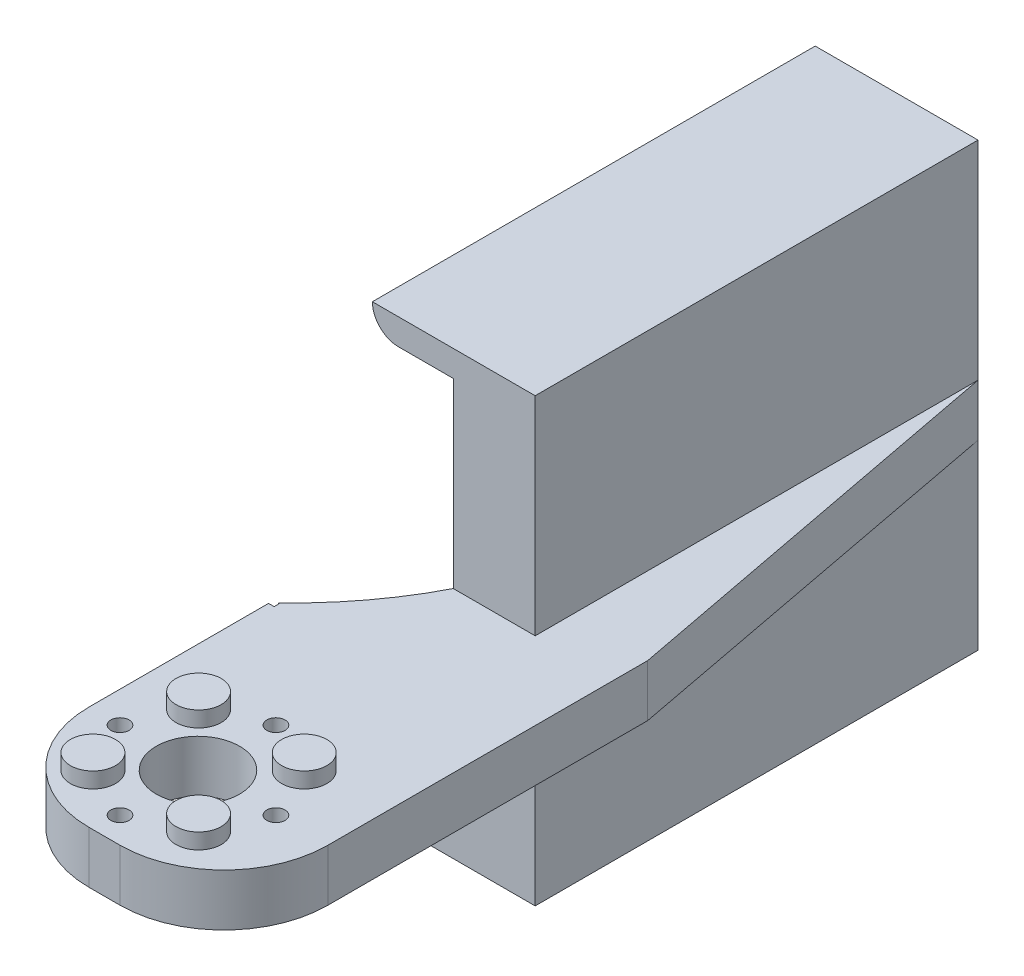
SolidWorks part; units mm, degrees
ref_plane "Front Plane" through (0, 0, 0) normal (0, 0, 1) x (1, 0, 0)
ref_plane "Top Plane" through (0, 0, 0) normal (0, 1, 0) x (1, 0, 0)
ref_plane "Right Plane" through (0, 0, 0) normal (1, 0, 0) x (0, 0, -1)
sketch "Sketch1" plane through (0, 0, 0) normal (0, 1, 0) x (1, 0, 0)
  line L1 (-25, 70) -> (25, 70)
  line L2 (-25, 70) -> (-25, -70)
  line L3 (-25, -70) -> (25, -70)
  line L4 (25, 70) -> (25, -70)
  dimension "D1" = 140
  dimension "D2" = 50
  dimension "D3" = 25
  dimension "D4" = 70
extrude "Boss-Extrude1" add sketch "Sketch1" along normal blind 10
sketch "Sketch2" plane through (0, 10, 0) normal (0, 1, 0) x (1, 0, 0)
  circle A4 centre (-14.25, 0) radius 4.35
  dimension "D1" = 8.7
  dimension "D2" = 14.25
extrude "Boss-Extrude2" add sketch "Sketch2" along normal blind 3
pattern_circular "CirPattern2" count 8 over 360 about axis through (0.1221, 0, 0) along (0, 1, 0) of "Boss-Extrude2"
sketch "Sketch4" plane through (0, 13, 0) normal (0, 1, 0) x (1, 0, 0)
  circle A0 centre (-14.25, 0) radius 4.575
  circle A1 centre (14.4941, 0) radius 4.575
  circle A2 centre (0.1221, -14.3721) radius 4.575
  circle A3 centre (0.1221, 14.3721) radius 4.575
extrude "Cut-Extrude3" cut sketch "Sketch4" against normal blind 3
sketch "Sketch5" plane through (0, 0, -70) normal (0, 0, -1) x (-1, 0, 0)
  line L1 (-25, 10) -> (25, 10)
  line L2 (-25, 10) -> (-25, 0)
  line L3 (-25, 0) -> (25, 0)
  line L4 (25, 10) -> (25, 0)
extrude "Boss-Extrude3" add sketch "Sketch5" along normal blind 70
sketch "Sketch6" plane through (0, 10, 0) normal (0, 1, 0) x (1, 0, 0)
  line L0 (-25, 140) -> (-25, -70) construction
  line L1 (25, -70) -> (-25, -70)
  line L2 (25, -70) -> (25, -20)
  line L3 (25, -20) -> (-25, -20)
  line L4 (-25, -70) -> (-25, -20)
  dimension "D1" = 50
extrude "Cut-Extrude4" cut sketch "Sketch6" against normal blind 10
sketch "Sketch7" plane through (0, 10, 0) normal (0, 1, 0) x (1, 0, 0)
  circle A0 centre (15, 0) radius 1.75
  circle A1 centre (-15, 0) radius 1.75
  circle A2 centre (0, 15) radius 1.75
  circle A3 centre (0, -15) radius 1.75
  dimension "D1" = 3.5
  dimension "D2" = 3.5
  dimension "D3" = 15
  dimension "D4" = 15
  dimension "D5" = 3.5
  dimension "D6" = 15
  dimension "D7" = 3.5
  dimension "D8" = 15
extrude "Cut-Extrude5" cut sketch "Sketch7" against normal blind 10
sketch "Sketch8" plane through (0, 10, 0) normal (0, 1, 0) x (1, 0, 0)
  line L0 (-25, 140) -> (25, 140) construction
  line L1 (-25, -20) -> (-21, -20)
  line L2 (-25, -20) -> (-25, 140)
  line L3 (-25, 140) -> (-21, 140)
  line L4 (-21, -20) -> (-21, 140)
  dimension "D1" = 4
extrude "Cut-Extrude6" cut sketch "Sketch8" against normal blind 10
sketch "Sketch9" plane through (0, 0, 0) normal (0, -1, 0) x (-1, 0, 0)
  line L0 (-10.0516, 140) -> (-25, 61.5056)
  line L1 (-25, 140) -> (21, 140) construction
  line L2 (-25, -20) -> (-25, 140) construction
  line L3 (-25, 61.5056) -> (-25, 140)
  line L4 (-25, 140) -> (-10.0516, 140)
extrude "Cut-Extrude10" cut sketch "Sketch9" against normal blind 10
sketch "Sketch10" plane through (0, 0, 0) normal (0, -1, 0) x (-1, 0, 0)
  line L1 (21, 34.8162) -> (21, 140)
  line L6 (21, -20) -> (21, 140) construction
  line L7 (-25, -20) -> (-25, 61.5056) construction
  arc A0 (21, 140) -> (21, 34.8162) centre (69, 87.4081) ccw
  dimension "D1" = 94
extrude "Cut-Extrude9" cut sketch "Sketch10" against normal blind 10
sketch "Sketch11" plane through (0, 10, 0) normal (0, 1, 0) x (1, 0, 0)
  line L1 (10.0516, 140) -> (-21.2653, 140)
  line L2 (10.0516, 140) -> (10.0516, 34.8162)
  line L3 (10.0516, 34.8162) -> (-21.2653, 34.8162)
  line L4 (-21.2653, 140) -> (-21.2653, 34.8162)
  point P5 (-21.2653, 39.6019)
  dimension "D1" = 0
  dimension "D2" = 31.317
extrude "Boss-Extrude4" add sketch "Sketch11" along normal blind 40
sketch "Sketch14" plane through (0, 50, 0) normal (0, 1, 0) x (1, 0, 0)
fillet "Fillet1" radius 20 1 edges at (25, 5, 20)
fillet "Fillet2" radius 20 1 edges at (-21, 5, 20)
sketch "Sketch16" plane through (0, 10, 0) normal (0, 1, 0) x (1, 0, 0)
  circle A0 centre (0, 0) radius 8
  dimension "D1" = 16
extrude "Cut-Extrude15" cut sketch "Sketch16" against normal blind 10
sketch "Sketch17" plane through (0, 10, 0) normal (0, -1, 0) x (-1, 0, 0)
  arc A0 (21, 140) -> (21, 34.8162) centre (69, 87.4081) ccw
extrude "Cut-Extrude17" cut sketch "Sketch17" against normal blind 35 and the other way through all
sketch "Sketch18" plane through (0, 0, 0) normal (0, -1, 0) x (-1, 0, 0)
  line L1 (-10.0516, 140) -> (21.2653, 140)
  line L2 (-10.0516, 140) -> (-10.0516, 34.8162)
  line L3 (-10.0516, 34.8162) -> (21.2653, 34.8162)
  line L4 (21.2653, 140) -> (21.2653, 34.8162)
extrude "Boss-Extrude6" add sketch "Sketch18" along normal blind 30
sketch "Sketch21" plane through (0, -30, 0) normal (0, -1, 0) x (-1, 0, 0)
  line L0 (-10.0516, 34.8162) -> (21.2653, 34.8162) construction
  arc A0 (21.2653, 140) -> (21.2653, 34.8162) centre (71.9043, 87.4081) ccw
extrude "Cut-Extrude20" cut sketch "Sketch21" against normal blind 30 and the other way through all
sketch "Sketch22" plane through (0, -30, 0) normal (0, -1, 0) x (-1, 0, 0)
  line L1 (-10.0516, 140) -> (20.6045, 140)
  line L2 (-10.0516, 140) -> (-10.0516, 35.1799)
  line L3 (-10.0516, 35.1799) -> (20.6045, 35.1799)
  line L4 (20.6045, 140) -> (20.6045, 35.1799)
  arc A0 (21, 140) -> (21, 34.8162) centre (69, 87.4081) ccw construction
extrude "Boss-Extrude7" add sketch "Sketch22" along normal blind 5
sketch "Sketch23" plane through (0, 50, 0) normal (0, 1, 0) x (1, 0, 0)
  line L0 (-21.2653, 140) -> (-21.2653, 34.8162) construction
  line L1 (10.0516, 34.8162) -> (-21.2653, 34.8162)
  line L2 (10.0516, 34.8162) -> (10.0516, 54.8162)
  line L3 (10.0516, 54.8162) -> (-21.2653, 54.8162)
  line L4 (-21.2653, 34.8162) -> (-21.2653, 54.8162)
  dimension "D1" = 20
extrude "Cut-Extrude21" cut sketch "Sketch23" against normal blind 40
sketch "Sketch24" plane through (0, -35, 0) normal (0, -1, 0) x (-1, 0, 0)
  line L0 (20.6045, 35.1799) -> (20.6045, 140) construction
  line L1 (-10.0516, 34.8162) -> (20.6045, 34.8162)
  line L2 (-10.0516, 34.8162) -> (-10.0516, 54.8162)
  line L3 (-10.0516, 54.8162) -> (20.6045, 54.8162)
  line L4 (20.6045, 34.8162) -> (20.6045, 54.8162)
  line L7 (-10.0516, 34.8162) -> (21.2653, 34.8162) construction
  dimension "D1" = 20
  dimension "D2" = 0
extrude "Cut-Extrude22" cut sketch "Sketch24" against normal blind 35
sketch "Sketch25" plane through (0, -30, 0) normal (0, -1, 0) x (-1, 0, 0)
  line L1 (19.9214, 34.5734) -> (21.7603, 34.5734)
  line L2 (19.9214, 34.5734) -> (19.9214, 35.6417)
  line L3 (19.9214, 35.6417) -> (21.7603, 35.6417)
  line L4 (21.7603, 34.5734) -> (21.7603, 35.6417)
extrude "Cut-Extrude23" cut sketch "Sketch25" against normal blind 40
fillet "Fillet3" radius 5 1 edges at (-21.2653, 45, -97.4081)
fillet "Fillet4" radius 5 1 edges at (-20.6045, -30, -97.0859)
